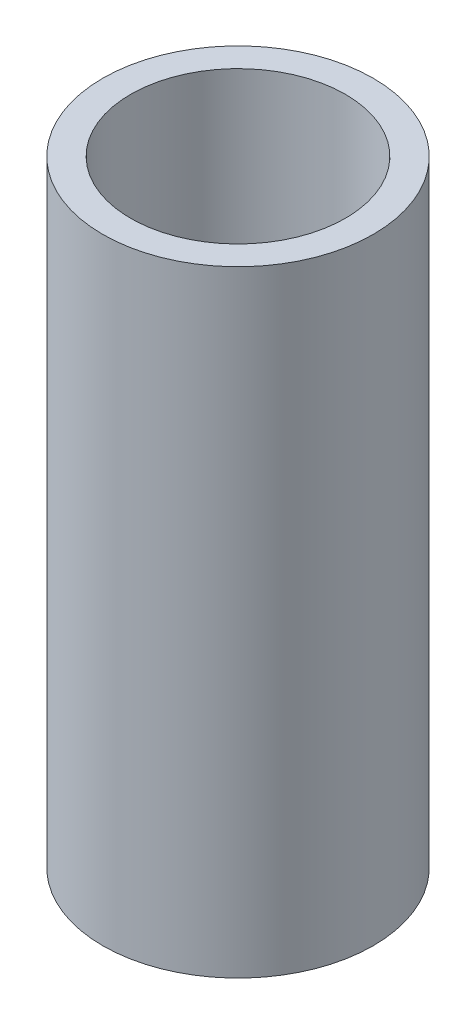
SolidWorks part; units mm, degrees
ref_plane "Front Plane" through (0, 0, 0) normal (0, 0, 1) x (1, 0, 0)
ref_plane "Top Plane" through (0, 0, 0) normal (0, 1, 0) x (1, 0, 0)
ref_plane "Right Plane" through (0, 0, 0) normal (1, 0, 0) x (0, 0, -1)
sketch "Sketch1" plane through (0, 0, 0) normal (0, 1, 0) x (1, 0, 0)
  circle A0 centre (0, 0) radius 25
  dimension "SLEEVE_OD" = 50
extrude "Boss-Extrude1" add sketch "Sketch1" along normal blind 113.8798
sketch "Sketch2" plane through (0, 0, 0) normal (0, 1, 0) x (1, 0, 0)
  circle A0 centre (0, 0) radius 19.8554
  dimension "BORE_D" = 39.7108
extrude "Cut-Extrude1" cut sketch "Sketch2" along normal through all
chamfer "Chamfer1" distance 3.638 angle 45 rebuild error yes
